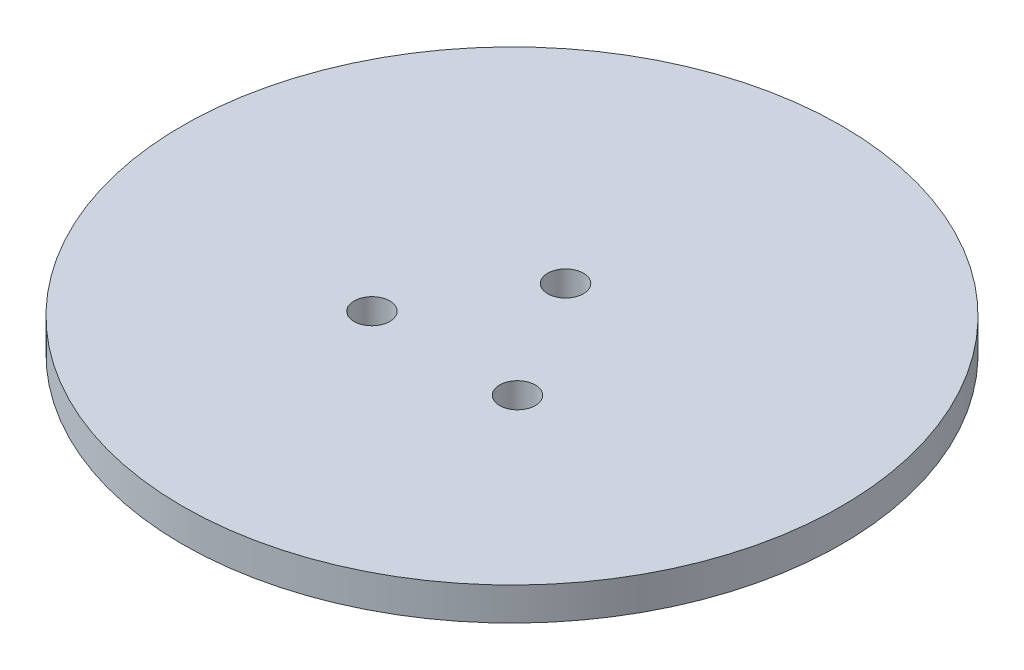
SolidWorks part; units mm, degrees
ref_plane "Front Plane" through (0, 0, 0) normal (0, 0, 1) x (1, 0, 0)
ref_plane "Top Plane" through (0, 0, 0) normal (0, 1, 0) x (1, 0, 0)
ref_plane "Right Plane" through (0, 0, 0) normal (1, 0, 0) x (0, 0, -1)
sketch "Sketch1" plane through (0, 0, 0) normal (0, 1, 0) x (1, 0, 0)
  line L0 (-59.1648, -12.192) -> (66.8918, -12.192) construction
  circle A0 centre (0, 0) radius 60.96
  circle A1 centre (-0.254, 10.16) radius 3.302
  circle A2 centre (-13.716, -12.192) radius 3.302
  circle A3 centre (13.208, -12.192) radius 3.302
  circle A4 centre (0, 0) radius 13.335 construction
  dimension "D1" = 121.92
  dimension "D2" = 6.604
  dimension "D3" = 6.604
  dimension "D4" = 6.604
  dimension "D5" = 26.67
  dimension "D6" = 13.716
  dimension "D9" = 10.16
  dimension "D10" = 12.192
  dimension "D11" = 0.254
  dimension "D8" = 13.208
extrude "Extrude1" add sketch "Sketch1" along normal blind 6.096
equation "\"MATERIAL\"=0.24"
equation "\"D1@Extrude1\" = \"MATERIAL\""
equation "\"mountingHole\"= .26"
equation "\"D2@Sketch1\" = \"mountingHole\""
equation "\"D3@Sketch1\" = \"mountingHole\""
equation "\"D4@Sketch1\" = \"mountingHole\""
